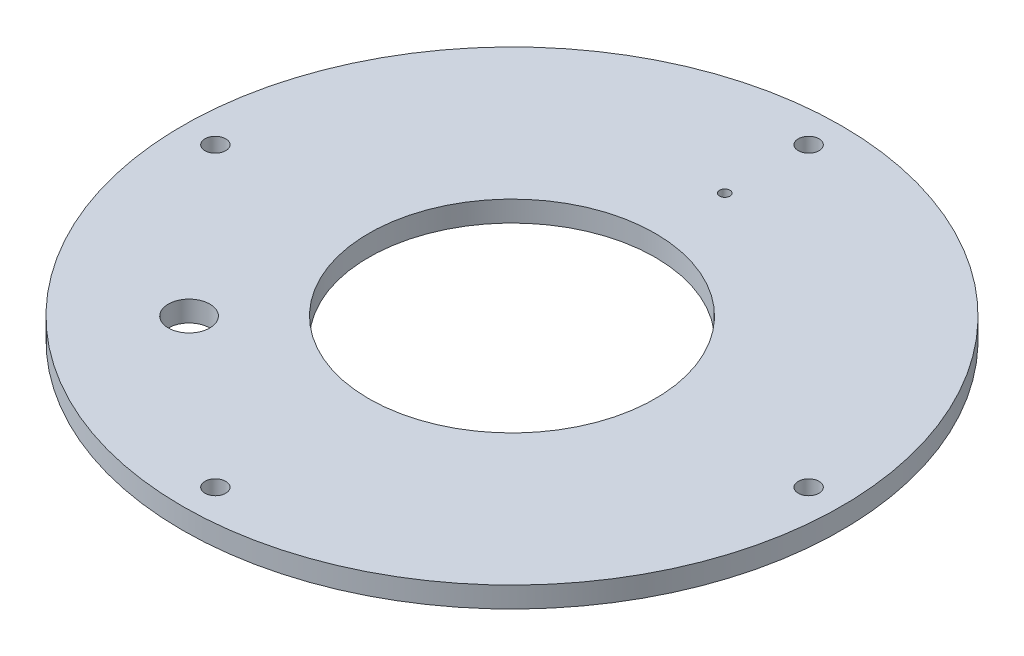
SolidWorks part; units mm, degrees
material "1060 Alloy"
ref_plane "Front Plane" through (0, 0, 0) normal (0, 0, 1) x (1, 0, 0)
ref_plane "Top Plane" through (0, 0, 0) normal (0, 1, 0) x (1, 0, 0)
ref_plane "Right Plane" through (0, 0, 0) normal (1, 0, 0) x (0, 0, -1)
sketch "Sketch1" plane through (0, 0, 0) normal (0, 1, 0) x (1, 0, 0)
  circle A0 centre (0, 0) radius 15.875
  circle A1 centre (0, 0) radius 6.9
  dimension "D1" = 31.75
  dimension "D2" = 13.8
extrude "Boss-Extrude1" add sketch "Sketch1" along normal blind 1
hole_wizard "CSK for M2 Flat Head Machine Screw1" positions "Sketch2" profile "Sketch3" countersink size "M2" standard "ANSI Metric" end condition through all
sketch "Sketch2" plane through (0, 0, 0) normal (0, -1, 0) x (-1, 0, 0)
  point P0 (0, -14.29)
  point P2 (-14.29, 0)
  point P4 (0, 14.29)
  point P28 (14.29, 0)
  dimension "D1" = 14.29
  dimension "D2" = 14.29
  dimension "D3" = 14.29
  dimension "D4" = 14.29
sketch "Sketch3" plane through (0, 0, 14.29) normal (1, 0, 0) x (0, 0, -1)
  line L0 (0, 0) -> (0, 1)
  line L1 (0, 1) -> (0.5, 1)
  line L2 (0.5, 1) -> (0.5, 0.2517)
  line L3 (0.5, 0.2517) -> (0.8, 0)
  line L5 (0.8, 0) -> (0, 0)
  line L6 (-0.5, 0.2517) -> (-0.8, 0) construction
  line L11 (0, -6.35) -> (0, 107.95) construction
  dimension "Thru Hole Dia." = 1
  dimension "Thru Hole Depth" = 1
  dimension "Near C'Sink Dia." = 1.6
  dimension "Near C'Sink Angle" = 100
sketch "Sketch4" plane through (0, 1, 0) normal (0, 1, 0) x (1, 0, 0)
  line L0 (0, 0) -> (-13.4332, -13.4332) construction
  circle A0 centre (0, 10.25) radius 0.25
  circle A1 centre (-7.7782, -7.7782) radius 1
  dimension "D1" = 0.5
  dimension "D2" = 10.25
  dimension "D4" = 2
  dimension "D3" = 11
  dimension "D5" = 0
extrude "Cut-Extrude1" cut sketch "Sketch4" against normal through all both and the other way through all
